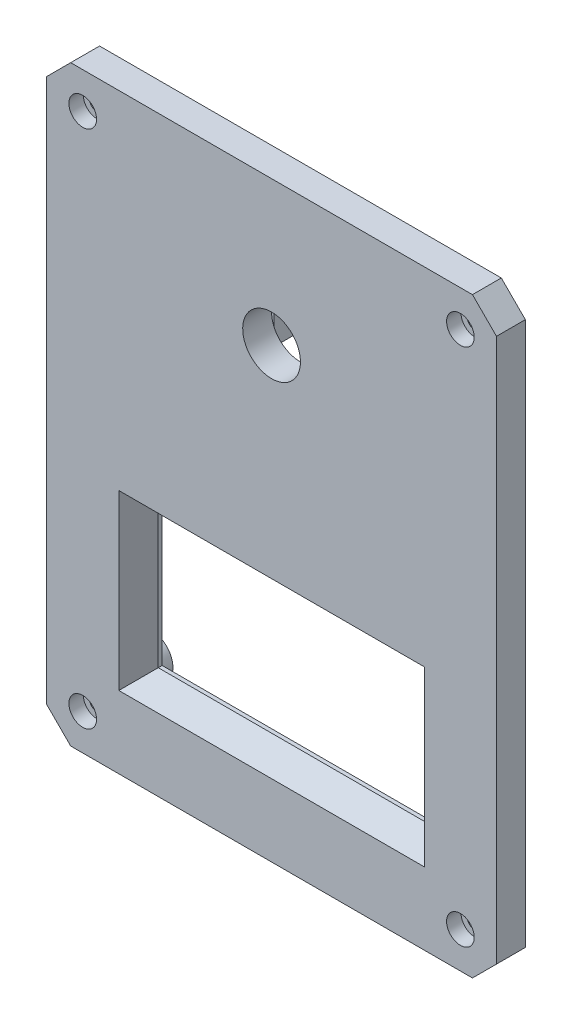
SolidWorks part; units mm, degrees
ref_plane "Front Plane" through (0, 0, 0) normal (0, 0, 1) x (1, 0, 0)
ref_plane "Top Plane" through (0, 0, 0) normal (0, 1, 0) x (1, 0, 0)
ref_plane "Right Plane" through (0, 0, 0) normal (1, 0, 0) x (0, 0, -1)
sketch "Sketch1" plane through (0, 0, 0) normal (0, 0, 1) x (1, 0, 0)
  line L0 (0, 89.3483) -> (0, -89.3483) construction
  line L1 (-65.6205, 89.3483) -> (65.6205, 89.3483) construction
  line L2 (-65.6205, 89.3483) -> (-65.6205, -89.3483) construction
  line L3 (-65.6205, -89.3483) -> (65.6205, -89.3483) construction
  line L4 (65.6205, 89.3483) -> (65.6205, -89.3483) construction
  line L5 (-65.6205, 0) -> (65.6205, 0) construction
  line L6 (28.75, -15) -> (-28.75, 15) construction
  line L7 (-28.75, 15) -> (28.75, 15)
  line L8 (-28.75, 15) -> (-28.75, -15)
  line L9 (-28.75, -15) -> (28.75, -15)
  line L10 (28.75, 15) -> (28.75, -15)
  line L12 (-46.75, -33) -> (46.75, -33)
  line L13 (-46.75, -33) -> (-46.75, 90)
  line L14 (-46.75, 90) -> (46.75, 90)
  line L15 (46.75, -33) -> (46.75, 90)
  circle A0 centre (0, 60) radius 6
  dimension "D3" = 12
  dimension "D1" = 57.5
  dimension "D2" = 30
  dimension "D4" = 60
  dimension "D5" = 30
  dimension "D6" = 18
  dimension "D7" = 18
  dimension "D8" = 18
extrude "Boss-Extrude1" add sketch "Sketch1" along normal blind 6
sketch "Sketch2" plane through (0, 0, 0) normal (0, 0, -1) x (-1, 0, 0)
  line L0 (0, 0) -> (0, -17.25) construction
  line L1 (34, -17.25) -> (-34, -17.25) construction
  line L2 (34, -17.25) -> (34, 21.75) construction
  line L3 (34, 21.75) -> (-34, 21.75) construction
  line L4 (-34, -17.25) -> (-34, 21.75) construction
  line L6 (0, 0) -> (0, 90) construction
  line L8 (0, 60) -> (8, 60) construction
  line L9 (8, 60) -> (8, 51.6) construction
  line L10 (5.5, 47.6) -> (5.5, 72.4)
  line L11 (5.5, 72.4) -> (13.5, 72.4)
  line L12 (13.5, 72.4) -> (13.5, 47.6)
  line L13 (13.5, 47.6) -> (5.5, 47.6)
  line L15 (-5.5, 54) -> (-10.5, 54)
  line L16 (-5.5, 54) -> (-5.5, 66)
  line L17 (-5.5, 66) -> (-10.5, 66)
  line L18 (-10.5, 54) -> (-10.5, 66)
  line L20 (-46.75, 90) -> (46.75, 90) construction
  circle A0 centre (34, -17.25) radius 2.1
  circle A1 centre (-34, -17.25) radius 2.1
  circle A2 centre (-34, 21.75) radius 2.1
  circle A3 centre (34, 21.75) radius 2.1
  circle A4 centre (34, -17.25) radius 4.5
  circle A5 centre (34, 21.75) radius 4.5
  circle A6 centre (-34, -17.25) radius 4.5
  circle A7 centre (-34, 21.75) radius 4.5
  circle A8 centre (8, 51.6) radius 2.1
  circle A9 centre (8, 68.4) radius 2.1
  point P19 (0, 90)
  point P35 (0, 0)
  point P36 (0, 41.7507)
  point P37 (0, 89.3483)
  point P41 (17.493, -6.0279)
  point P42 (28.75, -15)
  dimension "D1" = 4.2
  dimension "D2" = 4.2
  dimension "D3" = 4.2
  dimension "D4" = 4.2
  dimension "D8" = 9
  dimension "D9" = 9
  dimension "D10" = 4.2
  dimension "D17" = 11
  dimension "D5" = 68
  dimension "D6" = 39
  dimension "D7" = 2.25
  dimension "D11" = 8.4
  dimension "D12" = 8
  dimension "D13" = 2.5
  dimension "D14" = 8
  dimension "D15" = 4
  dimension "D16" = 4
  dimension "D18" = 5
  dimension "D19" = 12
  dimension "D20" = 6
extrude "Boss-Extrude2" add sketch "Sketch2" along normal blind 3 contours A5 A3 | A6 A1 | A4 A0 | A7 A2 region at (-29.6273, -17.25, 0) region at (-29.6273, 21.75, 0) region at (38.3727, -17.25, 0) region at (38.3727, 21.75, 0)
chamfer "Chamfer2" distance 5 angle 45 4 edges at (46.75, -33, 3) (-46.75, -33, 3) (-46.75, 90, 3) (46.75, 90, 3)
sketch "Sketch5" plane through (0, 0, 6) normal (0, 0, 1) x (1, 0, 0)
  line L0 (0, 0) -> (0, 79.1201) construction
  line L1 (46.75, -25.5) -> (39.25, -25.5) construction
  line L2 (46.75, -28) -> (46.75, 85) construction
  line L3 (39.25, -25.5) -> (39.25, -33) construction
  line L4 (-41.75, -33) -> (41.75, -33) construction
  line L5 (39.25, 90) -> (39.25, 82.5) construction
  line L6 (41.75, 90) -> (-41.75, 90) construction
  line L7 (39.25, 82.5) -> (46.75, 82.5) construction
  circle A0 centre (39.25, -25.5) radius 2.875
  circle A1 centre (39.25, 82.5) radius 2.875
  circle A2 centre (-39.25, -25.5) radius 2.875
  circle A3 centre (-39.25, 82.5) radius 2.875
  dimension "D1" = 5.75
  dimension "D4" = 5.75
  dimension "D2" = 7.5
  dimension "D3" = 7.5
  dimension "D5" = 7.5
  dimension "D6" = 7.5
extrude "Cut-Extrude2" cut sketch "Sketch5" against normal blind 3
sketch "Sketch6" plane through (0, 0, 3) normal (0, 0, 1) x (1, 0, 0)
  circle A0 centre (39.25, -25.5) radius 1.625
  circle A1 centre (-39.25, -25.5) radius 1.625
  circle A2 centre (-39.25, 82.5) radius 1.625
  circle A3 centre (39.25, 82.5) radius 1.625
  dimension "D1" = 3.25
  dimension "D2" = 3.25
  dimension "D3" = 3.25
  dimension "D4" = 3.25
extrude "Cut-Extrude3" cut sketch "Sketch6" against normal blind 23
sketch "Sketch7" plane through (0, 0, 0) normal (0, 0, 1) x (1, 0, 0)
  line L0 (0, 0) -> (0, -17.25) construction
  line L1 (34, -17.25) -> (-34, -17.25) construction
  line L2 (34, -17.25) -> (34, 21.75) construction
  line L3 (34, 21.75) -> (-34, 21.75) construction
  line L4 (-34, -17.25) -> (-34, 21.75) construction
  line L6 (0, 0) -> (0, 90) construction
  line L8 (0, 60) -> (8, 60) construction
  line L9 (8, 60) -> (8, 51.6) construction
  line L10 (5.5, 47.6) -> (5.5, 72.4)
  line L11 (5.5, 72.4) -> (13.5, 72.4)
  line L12 (13.5, 72.4) -> (13.5, 47.6)
  line L13 (13.5, 47.6) -> (5.5, 47.6)
  line L15 (-5.5, 54) -> (-10.5, 54)
  line L16 (-5.5, 54) -> (-5.5, 66)
  line L17 (-5.5, 66) -> (-10.5, 66)
  line L18 (-10.5, 54) -> (-10.5, 66)
  circle A0 centre (34, -17.25) radius 2.1
  circle A1 centre (-34, -17.25) radius 2.1
  circle A2 centre (-34, 21.75) radius 2.1
  circle A3 centre (34, 21.75) radius 2.1
  circle A4 centre (34, -17.25) radius 4.5
  circle A5 centre (34, 21.75) radius 4.5
  circle A6 centre (-34, -17.25) radius 4.5
  circle A7 centre (-34, 21.75) radius 4.5
  circle A8 centre (8, 51.6) radius 2.1
  circle A9 centre (8, 68.4) radius 2.1
  point P19 (0, 90)
  point P35 (0, 0)
  point P36 (0, 41.7507)
  point P37 (0, 89.3483)
  point P41 (17.493, -6.0279)
  point P42 (28.75, -15)
  dimension "D1" = 4.2
  dimension "D2" = 4.2
  dimension "D3" = 4.2
  dimension "D4" = 4.2
  dimension "D8" = 9
  dimension "D9" = 9
  dimension "D10" = 4.2
  dimension "D17" = 11
  dimension "D5" = 68
  dimension "D6" = 39
  dimension "D11" = 8.4
  dimension "D12" = 8
  dimension "D13" = 2.5
  dimension "D14" = 8
  dimension "D15" = 4
  dimension "D16" = 4
  dimension "D18" = 5
  dimension "D19" = 12
  dimension "D20" = 6
extrude "Boss-Extrude3" add sketch "Sketch7" against normal blind 6 contours L18 L15 L16 L17 | L13 L12 L11 L10 A8 A9 region at (9.7435, 60, 0) region at (-8, 60, 0)
chamfer "Chamfer3" distance 3 angle 60 4 edges at (0, 15, 6) (28.75, 0, 6) (0, -15, 6) (-28.75, 0, 6) first distance on face at (42.125, 82.5, 6)
sketch "Sketch9" plane through (0, 0, 0) normal (0, 0, -1) x (-1, 0, 0)
  line L0 (30, 45) -> (30, 75) construction
  line L1 (0, 60) -> (30, 60) construction
  line L2 (0, 60) -> (0, 62.8351) construction
  circle A0 centre (30, 75) radius 2.1
  circle A1 centre (30, 45) radius 2.1
  circle A2 centre (-30, 45) radius 2.1
  circle A3 centre (-30, 75) radius 2.1
  dimension "D1" = 4.2
  dimension "D2" = 4.2
  dimension "D3" = 30
  dimension "D4" = 30
extrude "Cut-Extrude5" cut sketch "Sketch9" against normal blind 3
